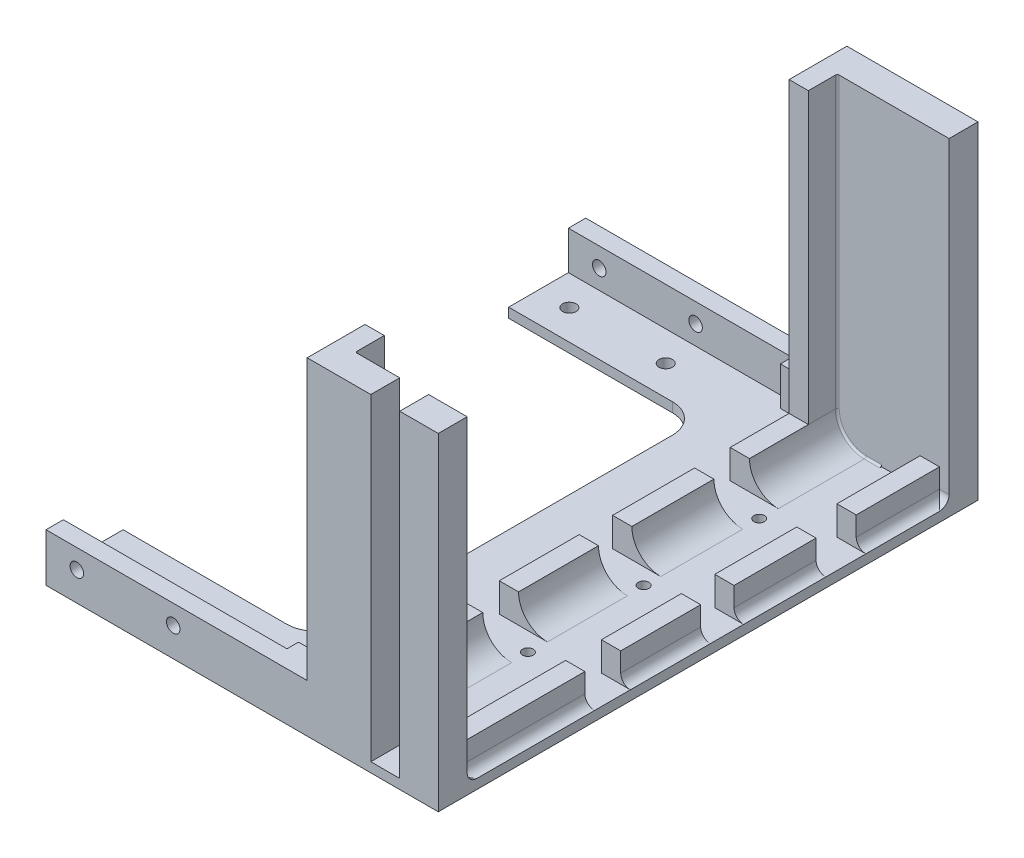
SolidWorks part; units mm, degrees
ref_plane "Front Plane" through (0, 0, 0) normal (0, 0, 1) x (1, 0, 0)
ref_plane "Top Plane" through (0, 0, 0) normal (0, 1, 0) x (1, 0, 0)
ref_plane "Right Plane" through (0, 0, 0) normal (1, 0, 0) x (0, 0, -1)
sketch "profile" plane through (0, 0, 0) normal (0, 0, 1) x (1, 0, 0)
  line L0 (11.8803, 7.4874) -> (14.5, 7.4874)
  line L1 (-5.5, 6.9749) -> (-7.8749, 4.6)
  line L2 (-7.8749, 4.6) -> (-12.1251, 4.6)
  line L3 (-12.1251, 4.6) -> (-14.5, 6.9749)
  line L4 (-8.1197, 7.4874) -> (-5.5, 7.4874)
  line L5 (-14.5, 6.9749) -> (-15.0126, 7.4874)
  line L6 (14.5, 6.9749) -> (12.1251, 4.6)
  line L7 (12.1251, 4.6) -> (7.8749, 4.6)
  line L8 (7.8749, 4.6) -> (5.5, 6.9749)
  line L9 (-14.7464, 10.3536) -> (-5.2536, 10.3536)
  line L10 (-14.5, 7.4874) -> (-11.8803, 7.4874)
  line L11 (5.5, 7.4874) -> (8.5334, 7.4874)
  line L12 (5.6673, 10.3536) -> (14.7464, 10.3536)
  line L13 (-15.0126, 7.4874) -> (-14.5, 7.4874)
  line L14 (-5.5, 6.9749) -> (-4.9874, 7.4874)
  line L15 (-4.9874, 7.4874) -> (-5.5, 7.4874)
  line L16 (5.5, 6.9749) -> (4.9874, 7.4874)
  line L17 (4.9874, 7.4874) -> (5.5, 7.4874)
  line L18 (14.5, 6.9749) -> (15.0126, 7.4874)
  line L19 (15.0126, 7.4874) -> (14.5, 7.4874)
  line L20 (-12.7464, 8.3536) -> (-14.7464, 10.3536)
  line L21 (-5.2536, 10.3536) -> (-7.2536, 8.3536)
  line L22 (7.6673, 8.3536) -> (5.6673, 10.3536)
  line L23 (14.7464, 10.3536) -> (12.7464, 8.3536)
  line L24 (-12.7464, 8.3536) -> (-11.8803, 7.4874)
  line L25 (-7.2536, 8.3536) -> (-8.1197, 7.4874)
  line L26 (7.6673, 8.3536) -> (8.5334, 7.4874)
  line L27 (12.7464, 8.3536) -> (11.8803, 7.4874)
  line L28 (-14.7464, 10.3536) -> (-20, 10.3536)
  line L29 (-20, 10.3536) -> (-20, 15.3536)
  line L30 (-20, 15.3536) -> (20, 15.3536)
  line L31 (20, 15.3536) -> (20, 10.3536)
  line L32 (20, 10.3536) -> (14.7464, 10.3536)
  line L33 (-5.2536, 10.3536) -> (5.6673, 10.3536)
  point P0 (-10, 4.6)
  point P1 (10, 4.6)
  dimension "D1" = 4.2503
  dimension "D2" = 5.7536
  dimension "D3" = 15.7497
  dimension "D4" = 20
  dimension "D5" = 5
extrude "Boss-Extrude1" add sketch "profile" along normal blind 250 contours L9 L33 L12 L32 L31 L30 L29 L28 region at (0, 12.8536, 0)
extrude "Boss-Extrude2" add sketch "Sketch1<3>" along normal blind 50 separate body contours L25 L21 L9 L20 L24 L10 L13 L5 L3 L2 L1 L14 L15 L4 | L27 L23 L12 L22 L26 L11 L17 L16 L8 L7 L6 L18 L19 L0 region at (10.0959, 7.5838, 0) region at (-10, 7.6238, 0)
sketch "Sketch1<3>" plane through (0, 0, 0) normal (0, 0, 1) x (1, 0, 0) same geometry as "profile"
pattern_linear "LPattern1" count 4 spacing 60 along (0, 0, 1) of "Boss-Extrude2"
sketch "Sketch2" plane through (0, 10.3536, 0) normal (0, -1, 0) x (1, 0, 0)
  line L0 (10, 250) -> (10, 0) construction
  line L1 (-20, 250) -> (20, 250) construction
  line L2 (12.1251, 0) -> (7.8749, 0) construction
  line L3 (-10, 230) -> (-10, 0) construction
  line L4 (-7.8749, 230) -> (-12.1251, 230) construction
  line L5 (-7.8749, 0) -> (-12.1251, 0) construction
  line L6 (-7.8749, 180) -> (-7.8749, 170) construction
  line L7 (-7.8749, 180) -> (-12.1251, 180) construction
  circle A0 centre (-10, 175) radius 2.75
  circle A1 centre (10, 175) radius 2.75
  circle A2 centre (-10, 115) radius 2.75
  circle A3 centre (10, 115) radius 2.75
  circle A4 centre (-10, 55) radius 2.75
  circle A5 centre (10, 55) radius 2.75
  point P21 (-7.8749, 175)
  dimension "D1" = 5.5
  dimension "D2" = 3
extrude "Cut-Extrude1" cut sketch "Sketch2" against normal through all
sketch "upper_acrylic_supp" plane through (0, 15.3536, 0) normal (0, 1, 0) x (1, 0, 0)
  line L0 (-20, 0) -> (20, 0) construction
  line L1 (-20, -250) -> (-34.5, -250) construction
  line L2 (-20, -250) -> (-20, 0) construction
  line L3 (-20, 0) -> (-34.5, 0) construction
  line L4 (-34.5, -250) -> (-34.5, 0) construction
  line L6 (-34.5, -250) -> (-24.5, -250)
  line L7 (-34.5, -250) -> (-34.5, -183.9264)
  line L8 (-34.5, -183.9264) -> (-24.5, -183.9264)
  line L9 (-24.5, -250) -> (-24.5, -183.9264)
  line L10 (-34.5, -165.3527) -> (-24.5, -165.3527)
  line L11 (-34.5, -165.3527) -> (-34.5, -123.8775)
  line L12 (-34.5, -123.8775) -> (-24.5, -123.8775)
  line L13 (-24.5, -165.3527) -> (-24.5, -123.8775)
  line L14 (-34.5, -106.5661) -> (-24.5, -106.5661)
  line L15 (-34.5, -106.5661) -> (-34.5, -64.0089)
  line L16 (-34.5, -64.0089) -> (-24.5, -64.0089)
  line L17 (-24.5, -106.5661) -> (-24.5, -64.0089)
  line L18 (-34.5, -45.5583) -> (-24.5, -45.5583)
  line L19 (-34.5, -45.5583) -> (-34.5, 0)
  line L20 (-34.5, 0) -> (-24.5, 0)
  line L21 (-24.5, -45.5583) -> (-24.5, 0)
  line L22 (-20, -250) -> (-40, -250)
  line L23 (-20, -250) -> (-20, 0)
  line L24 (-20, 0) -> (-40, 0)
  line L25 (-40, -250) -> (-40, 0)
  line M21 (-20, 0) -> (-20, -250)
  dimension "D1" = 5.5
  dimension "D2" = 10
  dimension "D3" = 20
extrude "Boss-Extrude3" add sketch "upper_acrylic_supp" against normal blind 5 contours L25 L22 L24 L21 L18 L19 L17 L14 L15 L16 L13 L10 L11 L12 L9 L6 L7 L8 M21 | L14 L17 L16 L15 | L10 L13 L12 L11 | L6 L9 L8 L7 | L18 L21 L20 L19 region at (-29.5, 15.3536, 216.9632) region at (-30.3215, 15.3536, 123.2164) region at (-29.5, 15.3536, 22.7792) region at (-29.5, 15.3536, 144.6151) region at (-29.5, 15.3536, 85.2875)
extrude "Boss-Extrude4" add sketch "upper_acrylic_supp<3>" along normal blind 15 contours L6 L9 L8 L7 | L10 L13 L12 L11 | L14 L17 L16 L15 | L18 L21 L20 L19 region at (-29.5, 15.3536, 216.9632) region at (-29.5, 15.3536, 22.7792) region at (-29.5, 15.3536, 144.6151) region at (-29.5, 15.3536, 85.2875)
sketch "upper_acrylic_supp<3>" plane through (0, 15.3536, 0) normal (0, 1, 0) x (1, 0, 0) same geometry as "upper_acrylic_supp"
fillet "Fillet1" radius 15 4 edges at (-24.5, 15.3536, 22.7792) (-24.5, 15.3536, 85.2875) (-24.5, 15.3536, 144.6151) (-24.5, 15.3536, 216.9632)
sketch "Sketch4" plane through (0, 15.3536, 0) normal (0, 1, 0) x (1, 0, 0)
  line L0 (20, -250) -> (20, 0) construction
  line L1 (-40, -250) -> (20, -250)
  line L2 (-40, -250) -> (-40, -265)
  line L3 (-40, -265) -> (20, -265)
  line L4 (20, -250) -> (20, -265)
  line L5 (-40, 0) -> (20, 0)
  line L6 (-40, 0) -> (-40, 15)
  line L7 (-40, 15) -> (20, 15)
  line L8 (20, 0) -> (20, 15)
  line L10 (-34.5, -265) -> (-34.5, 15) construction
  dimension "D1" = 15
  dimension "D2" = 15
extrude "Boss-Extrude5" add sketch "Sketch4" along normal mid plane 10
extrude "Boss-Extrude6" add sketch "Sketch4<3>" along normal blind 60
sketch "Sketch4<3>" plane through (0, 15.3536, 0) normal (0, 1, 0) x (1, 0, 0) same geometry as "Sketch4"
sketch "Sketch5" plane through (0, 0, 250) normal (0, 0, -1) x (-1, 0, 0)
  line L0 (-20, 75.3536) -> (40, 75.3536) construction
  line L1 (40, 15.3536) -> (34.5, 15.3536)
  line L2 (40, 15.3536) -> (40, 75.3536)
  line L3 (40, 75.3536) -> (34.5, 75.3536)
  line L4 (34.5, 15.3536) -> (34.5, 75.3536)
  line L6 (34.5, 15.3536) -> (24.5, 15.3536)
  line L7 (34.5, 15.3536) -> (34.5, 75.3536)
  line L8 (34.5, 75.3536) -> (24.5, 75.3536)
  line L9 (24.5, 15.3536) -> (24.5, 75.3536)
  line M5 (40, 75.3536) -> (-20, 75.3536)
  line M9 (24.5, 30.3536) -> (34.5, 30.3536)
  dimension "D1" = 5.5
  dimension "D2" = 10
extrude "Boss-Extrude7" add sketch "Sketch5" along normal blind 15 contours L9 L4 M9 M5 region at (-29.5, 52.8536, 250)
extrude "Boss-Extrude8" add sketch "Sketch5<3>" against normal blind 15 from surface contours L9 L4 M9 M5 region at (-29.5, 52.8536, 250) starting at face at (-18.2633, 33.7152, 0)
sketch "Sketch5<3>" plane through (0, 0, 250) normal (0, 0, -1) x (-1, 0, 0) same geometry as "Sketch5"
fillet "Fillet2" radius 1 6 edges at (5.25, 15.3536, 0) (-20.1066, 19.747, 0) (5.25, 15.3536, 250) (-20.1066, 19.747, 250) (-24.5, 52.8536, 0) (-24.5, 52.8536, 250)
sketch "Sketch6" plane through (-40, 0, 0) normal (-1, 0, 0) x (0, 0, 1)
  line L1 (250, 15.3536) -> (256, 15.3536)
  line L2 (250, 15.3536) -> (250, 75.3536)
  line L3 (250, 75.3536) -> (256, 75.3536)
  line L4 (256, 15.3536) -> (256, 75.3536)
  line L6 (0, 15.3536) -> (-6, 15.3536)
  line L7 (0, 15.3536) -> (0, 75.3536)
  line L8 (0, 75.3536) -> (-6, 75.3536)
  line L9 (-6, 15.3536) -> (-6, 75.3536)
  dimension "D1" = 6
  dimension "D2" = 6
extrude "Cut-Extrude2" cut sketch "Sketch6" against normal blind 6
sketch "Sketch7" plane through (-40, 0, 0) normal (-1, 0, 0) x (0, 0, 1)
  line L8 (265, 75.3536) -> (256, 75.3536)
  line L9 (256, 75.3536) -> (256, 15.3536)
  line L10 (256, 15.3536) -> (-6, 15.3536)
  line L11 (-6, 15.3536) -> (-6, 75.3536)
  line L12 (-6, 75.3536) -> (-15, 75.3536)
  line L13 (-15, 75.3536) -> (-15, 10.3536)
  line L14 (-15, 10.3536) -> (265, 10.3536)
  line L15 (265, 10.3536) -> (265, 75.3536)
  line L16 (265, 75.3536) -> (256, 75.3536)
  line L17 (256, 75.3536) -> (256, 15.3536)
  line L18 (256, 15.3536) -> (-6, 15.3536)
  line L19 (-6, 15.3536) -> (-6, 75.3536)
  line L20 (-6, 75.3536) -> (-15, 75.3536)
  line L21 (-15, 75.3536) -> (-15, 10.3536)
  line L22 (-15, 10.3536) -> (265, 10.3536)
  line L23 (265, 10.3536) -> (265, 75.3536)
  dimension "D1" = 0
extrude "Boss-Extrude9" add sketch "Sketch7" along normal blind 30
sketch "Sketch8" plane through (-70, 0, 0) normal (-1, 0, 0) x (0, 0, 1)
  line L0 (-15, 10.3536) -> (265, 10.3536) construction
  line L1 (-44.3745, 35.3536) -> (289.2282, 35.3536)
  line L2 (-44.3745, 35.3536) -> (-44.3745, 94.3849)
  line L3 (-44.3745, 94.3849) -> (289.2282, 94.3849)
  line L4 (289.2282, 35.3536) -> (289.2282, 94.3849)
  dimension "D1" = 25
extrude "Cut-Extrude3" cut sketch "Sketch8" against normal blind 150
sketch "Sketch9" plane through (-34, 0, 0) normal (-1, 0, 0) x (0, 0, 1)
  line L4 (256, 15.3536) -> (256, 35.3536)
  line L5 (256, 35.3536) -> (250, 35.3536)
  line L6 (250, 35.3536) -> (250, 15.3536)
  line L7 (250, 15.3536) -> (256, 15.3536)
  line L8 (256, 15.3536) -> (256, 35.3536)
  line L9 (256, 35.3536) -> (250, 35.3536)
  line L10 (250, 35.3536) -> (250, 15.3536)
  line L11 (250, 15.3536) -> (256, 15.3536)
  line L12 (0, 35.3536) -> (-6, 35.3536)
  line L13 (-6, 35.3536) -> (-6, 15.3536)
  line L14 (-6, 15.3536) -> (0, 15.3536)
  line L15 (0, 15.3536) -> (0, 35.3536)
  line L16 (0, 35.3536) -> (-6, 35.3536)
  line L17 (-6, 35.3536) -> (-6, 15.3536)
  line L18 (-6, 15.3536) -> (0, 15.3536)
  line L19 (0, 15.3536) -> (0, 35.3536)
  dimension "D1" = 0
  dimension "D2" = 0
extrude "cloth_escape_gap" add sketch "Sketch9" along normal blind 20
sketch "Sketch11" plane through (-70, 0, 0) normal (-1, 0, 0) x (0, 0, 1)
  line L0 (256, 35.3536) -> (256, 15.3536) construction
  line L1 (-15, 35.3536) -> (-6, 35.3536)
  line L2 (-15, 35.3536) -> (-15, 15.3536)
  line L3 (-15, 15.3536) -> (-6, 15.3536)
  line L4 (-6, 35.3536) -> (-6, 15.3536)
  line L5 (265, 35.3536) -> (256, 35.3536)
  line L6 (265, 35.3536) -> (265, 15.3536)
  line L7 (265, 15.3536) -> (256, 15.3536)
  line L8 (256, 35.3536) -> (256, 15.3536)
  line L9 (256, 15.3536) -> (256, 35.3536) construction
extrude "Boss-Extrude11" add sketch "Sketch11" along normal blind 100
sketch "Sketch12" plane through (0, 10.3536, 0) normal (0, -1, 0) x (1, 0, 0)
  line L0 (-70, -15) -> (-170, -10.5)
  line L1 (-170, -15) -> (-170, -6) construction
  line L2 (-170, -10.5) -> (-170, -15)
  line L3 (-170, -15) -> (-70, -15) construction
  line L4 (-170, -15) -> (-70, -15)
  line L5 (-70, 265) -> (-170, 260.5)
  line L6 (-170, 256) -> (-170, 265) construction
  line L7 (-170, 260.5) -> (-170, 265)
  line L8 (-170, 265) -> (-70, 265)
extrude "Cut-Extrude4" cut sketch "Sketch12" against normal blind 68 contours L8 L7 L5 | L0 L2 L4 region at (-136.6667, 10.3536, 263.5)
sketch "Sketch13" plane through (-70, 0, 0) normal (-1, 0, 0) x (0, 0, 1)
  line L0 (256, 15.3536) -> (265, 15.3536) construction
  line L1 (-15, 10.3536) -> (25, 10.3536)
  line L2 (-15, 10.3536) -> (-15, 15.3536)
  line L3 (-15, 15.3536) -> (25, 15.3536)
  line L4 (25, 10.3536) -> (25, 15.3536)
  line L5 (265, 10.3536) -> (225, 10.3536)
  line L6 (265, 10.3536) -> (265, 15.3536)
  line L7 (265, 15.3536) -> (225, 15.3536)
  line L8 (225, 10.3536) -> (225, 15.3536)
  line L9 (256, 15.3536) -> (-6, 15.3536) construction
  dimension "D1" = 40
  dimension "D2" = 40
extrude "Boss-Extrude13" add sketch "Sketch13" along normal blind 100
sketch "Sketch14" plane through (0, 15.3536, 0) normal (0, 1, 0) x (1, 0, 0)
  line L3 (-70, -265) -> (-170, -260.5)
  line L4 (-170, -260.5) -> (-170, -265)
  line L5 (-170, -265) -> (-70, -265)
  line L6 (-70, -265) -> (-170, -260.5)
  line L7 (-170, -260.5) -> (-170, -265)
  line L8 (-170, -265) -> (-70, -265)
  line L9 (-170, 15) -> (-170, 10.5)
  line L10 (-170, 10.5) -> (-70, 15)
  line L11 (-70, 15) -> (-170, 15)
  line L12 (-170, 15) -> (-170, 10.5)
  line L13 (-170, 10.5) -> (-70, 15)
  line L14 (-70, 15) -> (-170, 15)
  dimension "D1" = 0
  dimension "D2" = 0
extrude "Cut-Extrude5" cut sketch "Sketch14" against normal blind 100
fillet "Fillet3" radius 15 2 edges at (-70, 12.8536, 25) (-70, 12.8536, 225)
sketch "Sketch16" plane through (0, 15.3536, 0) normal (0, 1, 0) x (1, 0, 0)
  line L0 (20, -1) -> (-9.5, -1) construction
  line L1 (-34.5, -235) -> (18.5, -235) construction
  line L2 (-34.5, -235) -> (-34.5, -1) construction
  line L3 (-34.5, -1) -> (18.5, -1) construction
  line L4 (18.5, -235) -> (18.5, -1) construction
  line L5 (20, -265) -> (-70, -265) construction
  line L6 (18.5, -265) -> (33.5, -265)
  line L7 (18.5, -265) -> (18.5, 15)
  line L8 (18.5, 15) -> (33.5, 15)
  line L9 (33.5, -265) -> (33.5, 15)
  line L10 (-70, 15) -> (20, 15) construction
  line L11 (18.5, -250) -> (33.5, -250)
  line L12 (18.5, 0) -> (33.5, 0)
  line L13 (-23.5, -250) -> (20, -250) construction
  line L14 (-9.5, 0) -> (20, 0) construction
  line L15 (18.5, -250) -> (28.5, -250)
  line L16 (28.5, -250) -> (28.5, -183.9264)
  line L17 (28.5, 0) -> (18.5, 0)
  line L18 (18.5, -183.9264) -> (28.5, -183.9264)
  line L19 (18.5, -165.3527) -> (28.5, -165.3527)
  line L20 (18.5, -123.8775) -> (28.5, -123.8775)
  line L21 (18.5, -106.5661) -> (28.5, -106.5661)
  line L22 (18.5, -64.0089) -> (28.5, -64.0089)
  line L23 (18.5, -43.1778) -> (28.5, -43.1778)
  line L24 (-34.5, -165.3527) -> (-9.5, -165.3527) construction
  line L25 (-34.5, -183.9264) -> (-9.5, -183.9264) construction
  line L26 (-34.5, -106.5661) -> (-9.5, -106.5661) construction
  line L27 (-34.5, -123.8775) -> (-9.5, -123.8775) construction
  line L28 (-9.5, -64.0089) -> (-24.5, -64.0089) construction
  line L30 (28.5, -165.3527) -> (28.5, -123.8775)
  line L31 (28.5, -106.5661) -> (28.5, -64.0089)
  line L32 (28.5, -43.1778) -> (28.5, 0)
  line M38 (-9.5, -249) -> (20, -249)
  line M39 (20, -249) -> (20, -1)
  line M40 (20, -1) -> (-9.5, -1)
  dimension "D1" = 53
  dimension "D2" = 15
  dimension "D3" = 10
extrude "Boss-Extrude14" add sketch "Sketch16" along direction (0, -1, 0) on the side of the normal up to surface (20 mm away) from surface contours L7 L12 L9 L8 | L11 L7 L6 L9 region at (26, 15.3536, 257.5) region at (26, 15.3536, -7.5) up to face at (-51.6423, 35.3536, 251.8089) starting at face at (-10, 10.3536, 25)
extrude "Cut-Extrude6" cut sketch "Sketch16<5>" against normal blind 10 and the other way blind 30 contours L11 L7 L6 L9 | L32 L23 L22 L31 L21 L20 L30 L19 L18 L16 L11 L9 L12 M39 | L19 L30 L20 M39 | L21 L31 L22 M39 | L23 L32 L12 L7 M40 M39 | L7 L12 L9 L8 | L7 L23 M39 M40 | L23 L7 L22 M39 | L22 L7 L21 M39 | L21 L7 L20 M39 | L20 L7 L19 M39 | L19 L7 L18 M39 | L18 L7 M38 M39 | L18 L7 L11 L16 M39 M38 region at (26, 15.3536, 257.5) region at (24.2367, 15.3536, 217.0499) region at (29.1213, 15.3536, 121.3942) region at (19.25, 15.3536, 216.4632) region at (26, 15.3536, -7.5) region at (19.25, 15.3536, 174.6396) region at (24.2296, 15.3536, 21.5031) region at (19.25, 15.3536, 144.6151) region at (19.25, 15.3536, 115.2218) region at (24.25, 15.3536, 144.6151) region at (19.25, 15.3536, 22.0889) region at (19.25, 15.3536, 53.5934) region at (19.25, 15.3536, 85.2875) region at (24.25, 15.3536, 85.2875)
sketch "Sketch16<5>" plane through (0, 15.3536, 0) normal (0, 1, 0) x (1, 0, 0) same geometry as "Sketch16"
extrude "Boss-Extrude15" add sketch "Sketch16<6>" against normal up to surface (5 mm away) contours L32 L23 L22 L31 L21 L20 L30 L19 L18 L16 L11 L9 L12 M39 | L18 L7 L11 L16 M39 M38 | L11 L7 L6 L9 | L19 L30 L20 M39 | L21 L31 L22 M39 | L23 L32 L12 L7 M40 M39 | L7 L12 L9 L8 | L7 L23 M39 M40 | L23 L7 L22 M39 | L22 L7 L21 M39 | L21 L7 L20 M39 | L20 L7 L19 M39 | L19 L7 L18 M39 | L18 L7 M38 M39 region at (26, 15.3536, 257.5) region at (24.2367, 15.3536, 217.0499) region at (29.1213, 15.3536, 121.3942) region at (19.25, 15.3536, 216.4632) region at (26, 15.3536, -7.5) region at (19.25, 15.3536, 174.6396) region at (24.2296, 15.3536, 21.5031) region at (19.25, 15.3536, 144.6151) region at (19.25, 15.3536, 115.2218) region at (24.25, 15.3536, 144.6151) region at (19.25, 15.3536, 22.0889) region at (19.25, 15.3536, 53.5934) region at (19.25, 15.3536, 85.2875) region at (24.25, 15.3536, 85.2875) up to face at (-90.5656, 10.3536, 125)
sketch "Sketch16<6>" plane through (0, 15.3536, 0) normal (0, 1, 0) x (1, 0, 0) same geometry as "Sketch16"
extrude "Boss-Extrude16" add sketch "Sketch16<7>" along normal up to surface (20 mm away) contours L11 L7 L6 L9 | L7 L12 L9 L8 region at (26, 15.3536, 257.5) region at (26, 15.3536, -7.5) up to face at (-51.8923, 35.3536, 251.8089)
sketch "Sketch16<7>" plane through (0, 15.3536, 0) normal (0, 1, 0) x (1, 0, 0) same geometry as "Sketch16"
extrude "Boss-Extrude17" add sketch "Sketch16<8>" along normal up to surface (15 mm away) contours L18 L7 L11 L16 M39 M38 | L19 L30 L20 M39 | L21 L31 L22 M39 | L23 L32 L12 L7 M40 M39 | L7 L23 M39 M40 | L22 L7 L21 M39 | L20 L7 L19 M39 | L18 L7 M38 M39 region at (24.2367, 15.3536, 217.0499) region at (19.25, 15.3536, 216.4632) region at (24.2296, 15.3536, 21.5031) region at (19.25, 15.3536, 144.6151) region at (24.25, 15.3536, 144.6151) region at (19.25, 15.3536, 22.0889) region at (19.25, 15.3536, 85.2875) region at (24.25, 15.3536, 85.2875) up to face at (-29.5, 30.3536, 209.4632)
sketch "Sketch16<8>" plane through (0, 15.3536, 0) normal (0, 1, 0) x (1, 0, 0) same geometry as "Sketch16"
extrude "Boss-Extrude18" add sketch "Sketch14<2>" along normal up to surface (20 mm away) and the other way up to surface (5 mm away) up to face at (-49.3923, 35.3536, -1.8089) other way up to face at (-88.0656, 10.3536, 125)
sketch "Sketch14<2>" plane through (0, 15.3536, 0) normal (0, 1, 0) x (1, 0, 0) same geometry as "Sketch14"
fillet "Fillet4" radius 5 6 edges at (31, 15.3536, 250) (31, 15.3536, 0) (28.5, 15.3536, 21.5889) (28.5, 15.3536, 85.2875) (28.5, 15.3536, 144.6151) (28.5, 15.3536, 216.9632)
sketch "Sketch18" plane through (0, 35.3536, 0) normal (0, 1, 0) x (1, 0, 0)
  line L2 (-34.5, -250) -> (-34.5, -265)
  line L3 (-34.5, 15) -> (-34.5, 0)
  line L12 (-23.5, 0) -> (33.5, 0)
  line L13 (33.5, 0) -> (33.5, 15)
  line L14 (33.5, 15) -> (-170, 15)
  line L15 (-170, 15) -> (-170, 6)
  line L30 (-170, 6) -> (-54, 6)
  line L32 (-54, 6) -> (-54, 0)
  line L38 (-54, 0) -> (-34.5, 0)
  line L39 (-34.5, 0) -> (-34.5, -15)
  line L50 (-34.5, -15) -> (-24.5, -15)
  line L51 (-24.5, -15) -> (-24.5, -1)
  line L52 (-23.5, 0) -> (33.5, 0)
  line L53 (33.5, 0) -> (33.5, 15)
  line L54 (33.5, 15) -> (-34.5, 15)
  line L59 (-34.5, 0) -> (-34.5, -15)
  line L60 (-34.5, -15) -> (-24.5, -15)
  line L61 (-24.5, -15) -> (-24.5, -1)
  line L62 (-170, -265) -> (33.5, -265)
  line L63 (33.5, -265) -> (33.5, -250)
  line L64 (33.5, -250) -> (-23.5, -250)
  line L65 (-24.5, -249) -> (-24.5, -235)
  line L66 (-24.5, -235) -> (-34.5, -235)
  line L67 (-34.5, -235) -> (-34.5, -250)
  line L68 (-34.5, -250) -> (-54, -250)
  line L69 (-54, -250) -> (-54, -256)
  line L70 (-54, -256) -> (-170, -256)
  line L71 (-170, -256) -> (-170, -265)
  line L72 (-34.5, -265) -> (33.5, -265)
  line L73 (33.5, -265) -> (33.5, -250)
  line L74 (33.5, -250) -> (-23.5, -250)
  line L75 (-24.5, -249) -> (-24.5, -235)
  line L76 (-24.5, -235) -> (-34.5, -235)
  line L77 (-34.5, -235) -> (-34.5, -250)
  arc A5 (-23.5, 0) -> (-24.5, -1) centre (-23.5, -1) ccw
  arc A6 (-23.5, 0) -> (-24.5, -1) centre (-23.5, -1) ccw
  arc A7 (-24.5, -249) -> (-23.5, -250) centre (-23.5, -249) ccw
  arc A8 (-24.5, -249) -> (-23.5, -250) centre (-23.5, -249) ccw
  dimension "D1" = 0
  dimension "D2" = 0
extrude "Boss-Extrude21" add sketch "Sketch18" along normal blind 170 from surface starting at face at (-91.6787, 10.3536, 125)
sketch "Sketch19" plane through (0, 15.3536, 0) normal (0, 1, 0) x (1, 0, 0)
  line L0 (-170, -25) -> (-170, 6) construction
  line L1 (-70, -125) -> (-196.5165, -125) construction
  line L2 (-70, -210) -> (-70, -40) construction
  circle A0 centre (-154, -9.5) radius 3.5
  circle A1 centre (-104, -9.5) radius 3.5
  circle A2 centre (-104, -240.5) radius 3.5
  circle A3 centre (-154, -240.5) radius 3.5
  point P6 (-170, -9.5)
  dimension "D1" = 7
  dimension "D2" = 50
  dimension "D3" = 50
extrude "Cut-Extrude7" cut sketch "Sketch19" against normal blind 10
sketch "Sketch20" plane through (0, 0, 256) normal (0, 0, -1) x (-1, 0, 0)
  line L4 (34.5, 35.3536) -> (34.5, 15.3536)
  line L5 (34.5, 15.3536) -> (54, 15.3536)
  line L6 (54, 15.3536) -> (54, 35.3536)
  line L7 (54, 35.3536) -> (34.5, 35.3536)
  line L8 (34.5, 35.3536) -> (34.5, 15.3536)
  line L9 (34.5, 15.3536) -> (54, 15.3536)
  line L10 (54, 15.3536) -> (54, 35.3536)
  line L11 (54, 35.3536) -> (34.5, 35.3536)
  circle A0 centre (104, 25.3536) radius 3.5
  circle A1 centre (154, 25.3536) radius 3.5
  point P8 (54, 25.3536)
  point P9 (0, 0)
  dimension "D3" = 7
  dimension "D2" = 50
  dimension "D4" = 50
  dimension "D1" = 0
extrude "Cut-Extrude8" cut sketch "Sketch20" against normal blind 10 and the other way blind 355 contours A0 | A1 region at (-104, 25.3536, 256) region at (-154, 25.3536, 256)
sketch "Sketch21" plane through (0, 0, 0) normal (0, 0, 1) x (1, 0, 0)
  line L1 (13.5, 15.3536) -> (-1.5, 15.3536)
  line L2 (13.5, 15.3536) -> (13.5, 212.8546)
  line L3 (13.5, 212.8546) -> (-1.5, 212.8546)
  line L4 (-1.5, 15.3536) -> (-1.5, 212.8546)
  line L6 (18.5, 15.3536) -> (-9.5, 15.3536) construction
  line L7 (18.5, 30.3536) -> (18.5, 16.3536) construction
  point P4 (0, 0)
  point P6 (0, 0)
  point P8 (0, 0)
  dimension "D1" = 15
  dimension "D2" = 5
extrude "Cut-Extrude9" cut sketch "Sketch21" along normal blind 340
